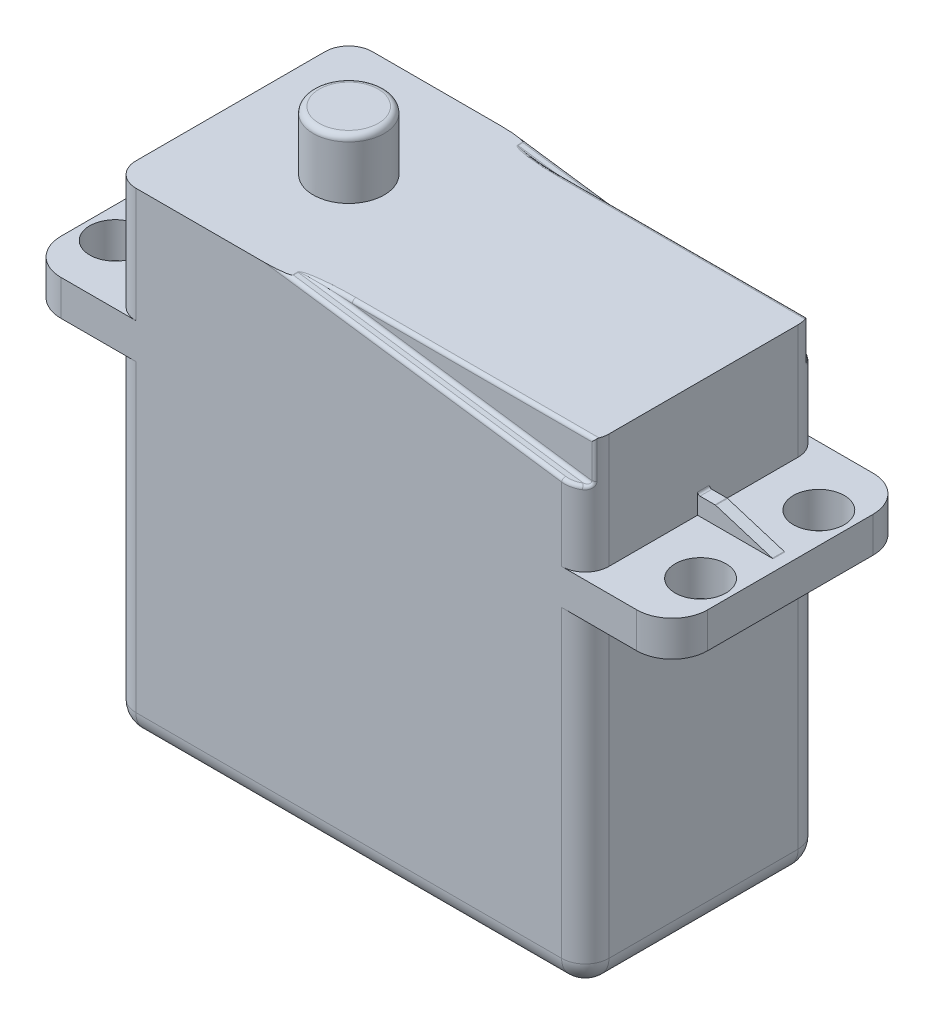
SolidWorks part; units mm, degrees
material "1060 合金"
ref_plane "正面" through (0, 0, 0) normal (0, 0, 1) x (1, 0, 0)
ref_plane "平面" through (0, 0, 0) normal (0, 1, 0) x (1, 0, 0)
ref_plane "右側面" through (0, 0, 0) normal (1, 0, 0) x (0, 0, -1)
sketch "ｽｹｯﾁ1" plane through (0, 0, 0) normal (0, 0, 1) x (1, 0, 0)
  line L1 (20, 20.2) -> (-20, 20.2)
  line L2 (20, 20.2) -> (20, -20.2)
  line L3 (20, -20.2) -> (-20, -20.2)
  line L4 (-20, 20.2) -> (-20, -20.2)
  line L5 (20, 20.2) -> (-20, -20.2) construction
  line L6 (20, -20.2) -> (-20, 20.2) construction
  point P0 (0, 0)
  dimension "D1" = 40
  dimension "D2" = 40.4
extrude "ﾎﾞｽ - 押し出し1" add sketch "ｽｹｯﾁ1" along normal blind 20
sketch "ｽｹｯﾁ2" plane through (0, 0, 20) normal (0, 0, 1) x (1, 0, 0)
  line L0 (-20, 20.2) -> (-20, -20.2) construction
  line L1 (-20, 10.5) -> (-27.35, 10.5)
  line L2 (-20, 10.5) -> (-20, 7.5)
  line L3 (-20, 7.5) -> (-27.35, 7.5)
  line L4 (-27.35, 10.5) -> (-27.35, 7.5)
  line L5 (0, 20.2) -> (0, 0) construction
  line L6 (20, 20.2) -> (-20, 20.2) construction
  line L7 (27.35, 10.5) -> (27.35, 7.5)
  line L8 (20, 7.5) -> (27.35, 7.5)
  line L9 (20, 10.5) -> (20, 7.5)
  line L10 (20, 10.5) -> (27.35, 10.5)
  line L11 (-20, -20.2) -> (20, -20.2) construction
  dimension "D1" = 54.7
  dimension "D2" = 27.7
  dimension "D3" = 3
extrude "ﾎﾞｽ - 押し出し2" add sketch "ｽｹｯﾁ2" against normal up to surface (20 mm away) up to face at (0, 0, 0)
sketch "ｽｹｯﾁ3" plane through (0, 10.5, 0) normal (0, 1, 0) x (1, 0, 0)
  line L0 (0, 0) -> (0, -20) construction
  line L1 (20, 0) -> (-20, 0) construction
  line L2 (20, -20) -> (-20, -20) construction
  line L3 (-27.35, -10) -> (0, -10) construction
  line L4 (-27.35, 0) -> (-27.35, -20) construction
  circle A0 centre (-24.75, -5) radius 2.15
  circle A1 centre (-24.75, -15) radius 2.15
  circle A2 centre (24.75, -15) radius 2.15
  circle A3 centre (24.75, -5) radius 2.15
  dimension "D1" = 49.5
  dimension "D2" = 4.3
  dimension "D3" = 10
extrude "ｶｯﾄ - 押し出し2" cut sketch "ｽｹｯﾁ3" against normal through all
fillet "ﾌｨﾚｯﾄ1" radius 3 4 edges at (27.35, 9, 20) (27.35, 9, 0) (-27.35, 9, 20) (-27.35, 9, 0)
ref_plane "平面1" through (0, 0, 10) normal (0, 0, -1) x (-1, 0, 0)
sketch "ｽｹｯﾁ4" plane through (0, 0, 10) normal (0, 0, -1) x (-1, 0, 0)
  line L0 (26.35, 10.5) -> (21.5, 12)
  line L1 (27.35, 10.5) -> (24.35, 10.5) construction
  line L2 (21.5, 12) -> (20, 12)
  line L3 (20, 20.2) -> (20, 10.5) construction
  line L4 (27.35, 7.5) -> (27.35, 10.5) construction
  line L5 (20, 10.5) -> (24.35, 10.5) construction
  line L6 (0, 20.2) -> (0, 0) construction
  line L7 (-20, 20.2) -> (20, 20.2) construction
  line L8 (26.35, 10.5) -> (20, 10.5)
  line L9 (20, 10.5) -> (20, 12)
  line L10 (-20, 10.5) -> (-20, 12)
  line L11 (-26.35, 10.5) -> (-20, 10.5)
  line L12 (-21.5, 12) -> (-20, 12)
  line L13 (-26.35, 10.5) -> (-21.5, 12)
  dimension "D1" = 1.5
  dimension "D2" = 1
  dimension "D3" = 1.5
extrude "ﾎﾞｽ - 押し出し3" add sketch "ｽｹｯﾁ4" along normal mid plane 1
fillet "ﾌｨﾚｯﾄ2" radius 2 8 edges at (-20, -6.35, 0) (-20, 15.35, 0) (20, -6.35, 0) (20, 15.35, 0) (20, 15.35, 20) (20, -6.35, 20) (-20, -6.35, 20) (-20, 15.35, 20)
fillet "ﾌｨﾚｯﾄ3" radius 2 8 edges at (-19.4142, -20.2, 19.4142) (-20, -20.2, 10) (-19.4142, -20.2, 0.5858) (0, -20.2, 0) (19.4142, -20.2, 0.5858) (20, -20.2, 10) (19.4142, -20.2, 19.4142) (0, -20.2, 20)
sketch "ｽｹｯﾁ5" plane through (0, 20.2, 0) normal (0, 1, 0) x (1, 0, 0)
  line L0 (-27.35, -10) -> (27.35, -10) construction
  line L1 (-27.35, -3) -> (-27.35, -17) construction
  line L2 (27.35, -3) -> (27.35, -17) construction
  line L3 (-20, -18) -> (-20, -2) construction
  circle A0 centre (-10, -10) radius 3
  dimension "D1" = 6
  dimension "D2" = 10
extrude "ﾎﾞｽ - 押し出し4" add sketch "ｽｹｯﾁ5" along normal blind 5
fillet "ﾌｨﾚｯﾄ4" radius 0.2 6 edges at (26.35, 10.5, 10) (21.5, 12, 10) (20, 12, 10) (-20, 12, 10) (-21.5, 12, 10) (-26.35, 10.5, 10)
fillet "ﾌｨﾚｯﾄ5" radius 0.5 1 edges at (-10, 25.2, 13)
sketch "ｽｹｯﾁ6" plane through (0, 0, 20) normal (0, 0, 1) x (1, 0, 0)
  line L0 (-5, 20.2) -> (20, 16.7)
  line L1 (18, 20.2) -> (-18, 20.2) construction
  line L2 (20, 20.2) -> (20, 10.5) construction
  line L3 (20, 16.7) -> (20, 20.2)
  line L4 (20, 20.2) -> (-5, 20.2)
  dimension "D1" = 25
  dimension "D2" = 3.5
extrude "ｶｯﾄ - 押し出し3" cut sketch "ｽｹｯﾁ6" against normal blind 1
mirror "ﾐﾗｰ1" about plane through (0, 0, 10) normal (0, 0, -1) of "ｶｯﾄ - 押し出し3"
fillet "ﾌｨﾚｯﾄ6" radius 0.3 12 edges at (19, 16.84, 19.7321) (6.5, 18.59, 20) (7.366, 20.2, 19) (19, 16.84, 0.2679) (6.5, 18.59, 0) (7.366, 20.2, 1) (-5, 20.2, 0.5) (-5, 20.2, 19.5) (7.366, 18.4688, 19) (19.7321, 18.4688, 19) (19.7321, 18.4688, 1) (7.366, 18.4688, 1)
